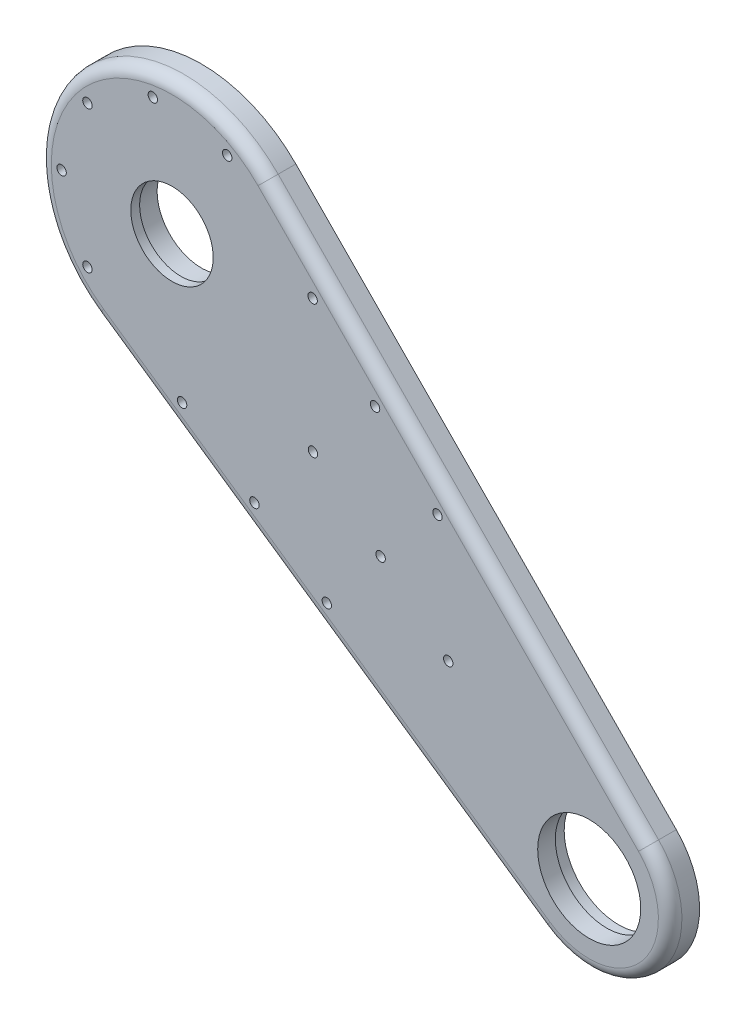
SolidWorks part; units mm, degrees
material "ABS"
ref_plane "Front Plane" through (0, 0, 0) normal (0, 0, 1) x (1, 0, 0)
ref_plane "Top Plane" through (0, 0, 0) normal (0, 1, 0) x (1, 0, 0)
ref_plane "Right Plane" through (0, 0, 0) normal (1, 0, 0) x (0, 0, -1)
ref_plane "Plane1" through (0, 0, 37) normal (0, 0, 1) x (1, 0, 0)
sketch "Sketch1" plane through (0, 0, 37) normal (0, 0, 1) x (1, 0, 0)
  line L1 (26.7138, 26.3177) -> (155.9656, -104.8796) construction
  line L2 (-25.5349, -37.0536) -> (126.1136, -141.5596)
  line L3 (32.0566, 31.5812) -> (161.3084, -99.6161)
  line L4 (-21.2791, -30.878) -> (130.3694, -135.384) construction
  line L5 (0, 0) -> (141.7182, -118.9157) construction
  arc A0 (32.0566, 31.5812) -> (-25.5349, -37.0536) centre (0, 0) ccw
  arc A1 (126.1136, -141.5596) -> (161.3084, -99.6161) centre (141.7182, -118.9157) ccw
  circle A5 centre (0, 0) radius 25 construction
  circle A6 centre (0, 0) radius 37.5 construction
  circle A7 centre (141.7182, -118.9157) radius 17.5
  circle A8 centre (70.8591, -59.4579) radius 1.6
  circle A9 centre (93.8404, -78.7415) radius 1.6
  circle A10 centre (47.8778, -40.1742) radius 1.6
  circle A11 centre (141.7182, -118.9157) radius 20 construction
  circle A12 centre (47.768, 4.9466) radius 1.6
  circle A14 centre (3.4233, -47.9013) radius 1.6
  circle A16 centre (68.9739, -16.2739) radius 1.6
  circle A17 centre (90.1797, -37.4944) radius 1.6
  circle A18 centre (28.0039, -65.1001) radius 1.6
  circle A19 centre (52.5844, -82.2989) radius 1.6
  circle A20 centre (116.8218, -98.0251) radius 1.6 construction
  circle A21 centre (0, 0) radius 25 construction
  circle A22 centre (141.7182, -118.9157) radius 17.5 construction
  point P16 (141.7182, -118.9157)
extrude "Boss-Extrude1" add sketch "Sketch1" along normal blind 10
sketch "Sketch2" plane through (0, 0, 37) normal (0, 0, -1) x (-1, 0, 0)
  circle A0 centre (-141.7182, -118.9157) radius 18.5
  dimension "D1" = 37
extrude "Cut-Extrude1" cut sketch "Sketch2" against normal blind 4
sketch "Sketch3" plane through (0, 0, 37) normal (0, 0, -1) x (-1, 0, 0)
  circle A0 centre (-18.75, 32.476) radius 1.6
  circle A1 centre (6.5118, 36.9303) radius 1.6
  circle A2 centre (28.7267, 24.1045) radius 1.6
  circle A3 centre (37.5, 0) radius 1.6
  circle A4 centre (28.7267, -24.1045) radius 1.6
  dimension "D1" = 3.2
  dimension "D2" = 3.2
  dimension "D3" = 3.2
  dimension "D4" = 3.2
  dimension "D5" = 3.2
extrude "Cut-Extrude2" cut sketch "Sketch3" against normal through all
sketch "Sketch4" plane through (0, 0, 37) normal (0, 0, -1) x (-1, 0, 0)
  circle A0 centre (0, 0) radius 14
  circle A1 centre (0, 0) radius 15.0625
  dimension "D1" = 28
  dimension "D2" = 30.125
extrude "Cut-Extrude3" cut sketch "Sketch4" against normal through all contours A0 region at (0, 0, 37)
extrude "Cut-Extrude4" cut sketch "Sketch4<3>" against normal blind 7 contours A1 A0 region at (14.6365, 0, 37)
sketch "Sketch4<3>" plane through (0, 0, 37) normal (0, 0, -1) x (-1, 0, 0) same geometry as "Sketch4"
fillet "Fillet1" radius 4 4 edges at (162.7844, -136.5924, 47) (50.2894, -89.3066, 47) (-34.472, 28.9254, 47) (96.6825, -34.0174, 47)
equation "\"thighLength\"=185"
equation "\"legLength\"=200"
equation "\"m3Thru\"=3.2"
equation "\"m4Thru\"=4.3"
equation "\"shoulder5mm\"=5.1"
equation "\"6706out\"=37.125"
equation "\"6706in\"=30"
equation "\"6904out\"=30.125"
equation "\"6904in\"=17"
equation "\"D1@Sketch3\"=\"m3Thru\""
equation "\"D2@Sketch3\"=\"m3Thru\""
equation "\"D3@Sketch3\"=\"m3Thru\""
equation "\"D4@Sketch3\"=\"m3Thru\""
equation "\"D5@Sketch3\"=\"m3Thru\""
equation "\"D2@Sketch4\"=\"6904out\""
